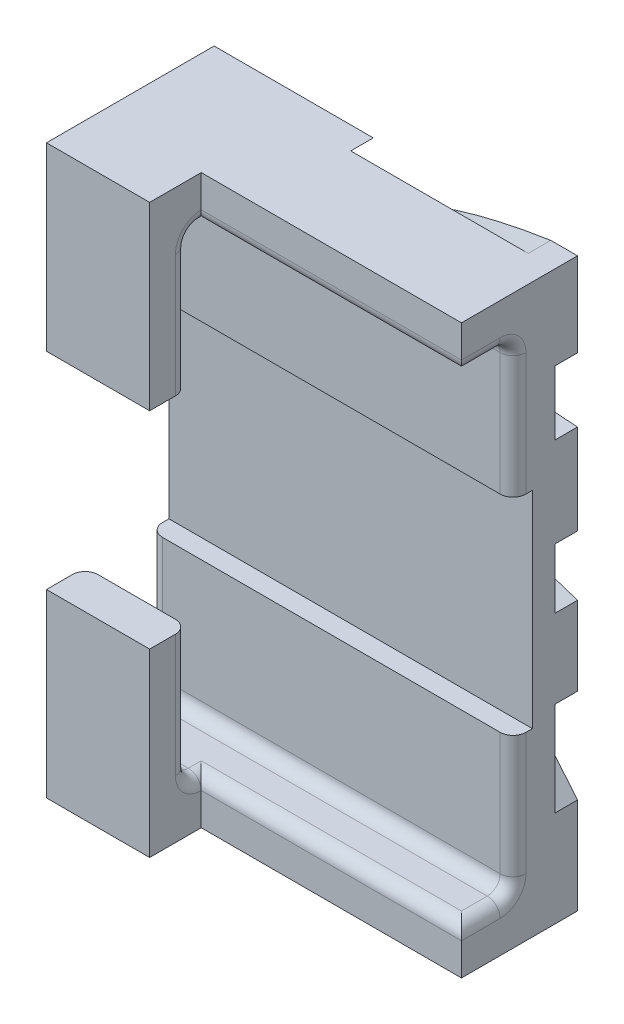
SolidWorks part; units mm, degrees
ref_plane "Front Plane" through (0, 0, 0) normal (0, 0, 1) x (1, 0, 0)
ref_plane "Top Plane" through (0, 0, 0) normal (0, 1, 0) x (1, 0, 0)
ref_plane "Right Plane" through (0, 0, 0) normal (1, 0, 0) x (0, 0, -1)
sketch "Sketch1" plane through (0, 0, 0) normal (0, 0, 1) x (1, 0, 0)
  line L1 (-14.09, -22) -> (14.09, -22)
  line L2 (-14.09, -22) -> (-14.09, 22)
  line L3 (-14.09, 22) -> (14.09, 22)
  line L4 (14.09, -22) -> (14.09, 22)
  line L5 (-14.09, -22) -> (14.09, 22) construction
  line L6 (-14.09, 22) -> (14.09, -22) construction
  point P0 (0, 0)
  dimension "D1" = 44
  dimension "D2" = 28.18
extrude "Boss-Extrude1" add sketch "Sketch1" along normal blind 11 and the other way blind 2
sketch "Sketch3" plane through (-14.09, 0, 0) normal (-1, 0, 0) x (0, 0, 1)
  line L0 (8, 8) -> (11, 8)
  line L5 (8, 18.5) -> (3, 18.5)
  line L6 (8, 18.5) -> (8, 8)
  line L7 (8, -18.5) -> (3, -18.5)
  line L8 (3, 18.5) -> (3, 8)
  line L9 (11, -8) -> (8, -8)
  line L10 (8, -8) -> (8, -18.5)
  line L13 (3, -8) -> (1.5034, -8)
  line L14 (11, 8) -> (11, -8)
  line L15 (14.8907, 0) -> (-5.9971, 0) construction
  line L16 (3, 8) -> (1.5034, 8)
  line L17 (1.5034, 8) -> (1.5034, -8)
  line L18 (3, -8) -> (3, -18.5)
  dimension "D1" = 3
  dimension "D2" = 5
  dimension "D3" = 37
extrude "Cut-Extrude1" cut sketch "Sketch3" against normal blind 37
sketch "Sketch4" plane through (0, -22, 0) normal (0, -1, 0) x (1, 0, 0)
  line L0 (-14.09, 11) -> (14.09, 11) construction
  line L1 (-6.09, 11) -> (14.09, 11)
  line L2 (-6.09, 11) -> (-6.09, 7)
  line L3 (-6.09, 7) -> (14.09, 7)
  line L4 (14.09, 11) -> (14.09, 7)
  line L5 (14.09, -2) -> (14.09, 11) construction
  line L6 (-14.09, -2) -> (-14.09, 11) construction
  dimension "D1" = 4
  dimension "D2" = 8
extrude "Cut-Extrude2" cut sketch "Sketch4" against normal blind 48
sketch "Sketch5" plane through (0, 0, -2) normal (0, 0, -1) x (-1, 0, 0)
  line L0 (14.09, 4.4317) -> (14.09, 4.2995)
  line L1 (-14.09, 22) -> (14.09, 22) construction
  line L2 (1.7471, 22) -> (-12.0158, 22)
  line L3 (14.09, 4.4317) -> (14.09, 4.2995)
  line L4 (6.9247, -22) -> (1.3985, -22)
  line L5 (-14.09, 15.483) -> (-14.09, 10.5052)
  line L6 (1.7471, 22) -> (-12.0158, 22)
  line L7 (6.9247, -22) -> (1.3985, -22)
  line L8 (-4.8324, -22) -> (-9.4224, -22)
  line L9 (-14.09, 15.483) -> (-14.09, 10.5052)
  line L10 (-14.09, 3.5233) -> (-14.09, -1.1313)
  line L11 (-14.09, -7.2405) -> (-14.09, -14.5457)
  line L12 (-4.8324, -22) -> (-9.4224, -22)
  line L13 (14.09, 22) -> (14.09, -22) construction
  line L14 (14.09, -22) -> (-14.09, -22) construction
  spline S0 degree 3 poles (1.7471, 22) (22.5217, 10.8459) (6.4841, -7.6222) (6.9247, -22) knots 0 0 0 0 0.832841 0.832841 0.832841 0.832841
  spline S1 degree 3 poles (-12.0158, 22) (19.8935, 17.1686) (4.9435, -4.8632) (1.3985, -22) knots 0 0 0 0 0.886772 0.886772 0.886772 0.886772
  spline S2 degree 3 poles (-14.09, 15.483) (19.4581, 15.6043) (-0.2323, -5.6377) (-4.8324, -22) knots 0 0 0 0 0.882154 0.882154 0.882154 0.882154
  spline S3 degree 3 poles (-14.09, 10.5052) (15.4705, 12.9607) (-5.2505, -7.0269) (-9.4224, -22) knots 0 0 0 0 0.871233 0.871233 0.871233 0.871233
  spline S4 degree 2 poles (-14.09, 3.5233) (7.9134, 11.6377) (-14.09, -14.5457) knots 0 0 0 1 1 1
  spline S5 degree 2 poles (-14.09, -1.1313) (-1.6541, 3.2119) (-14.09, -7.2405) knots 0 0 0 1 1 1
  line M1 (-14.09, 22) -> (-14.09, -22)
  line M2 (-14.09, -22) -> (14.09, -22)
  line M4 (14.09, 22) -> (-14.09, 22)
extrude "Cut-Extrude3" cut sketch "Sketch5" against normal blind 1.75 contours S3 S2 M1 M2 | S5 S4 M1 | S1 S0 M4 M2 region at (-11.5732, 1.9508, -2) region at (7.1274, -21.5789, -2) region at (4.526, -0.8216, -2)
fillet "Fillet1" radius 1 20 edges at (-14.09, -13.25, 3) (-14.09, -13.25, 8) (14.09, -13.25, 3) (-6.09, -13.25, 8) (14.09, 13.25, 3) (-14.09, 13.25, 3) (-14.09, 13.25, 8) (-6.09, 13.25, 8) (-14.09, -18.5, 5.5) (0, -18.5, 3) (14.09, -18.5, 5) (4, -18.5, 7) (-6.09, -18.5, 7.5) (-10.09, -18.5, 8) (14.09, 18.5, 5) (0, 18.5, 3) (-14.09, 18.5, 5.5) (-10.09, 18.5, 8) (-6.09, 18.5, 7.5) (4, 18.5, 7)
